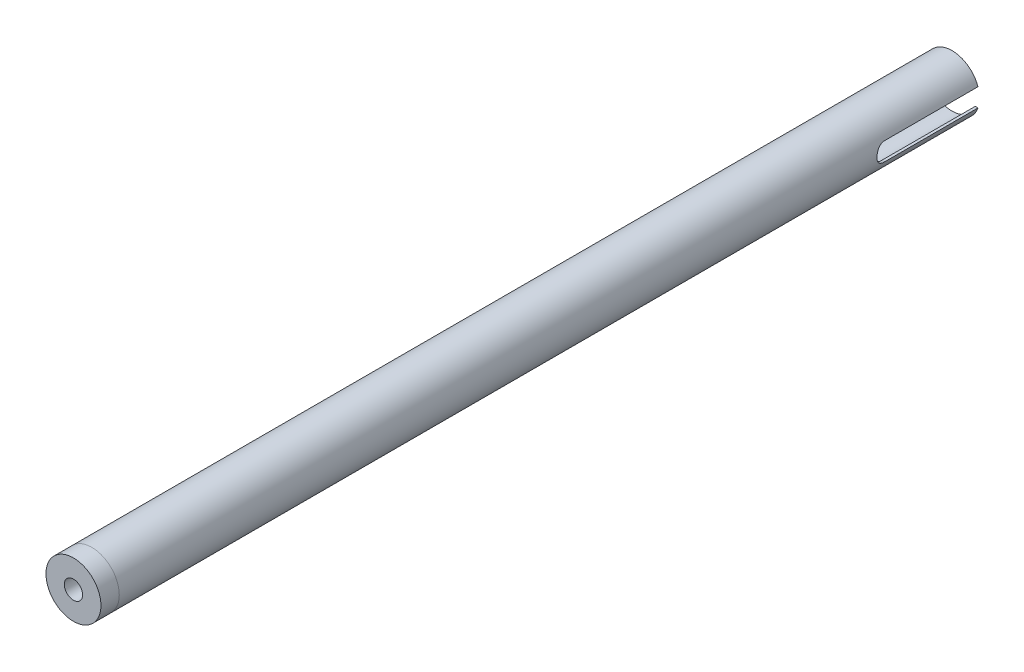
SolidWorks part; units mm, degrees
material "AISI 4130 Steel, normalized at 870C"
ref_plane "Front Plane" through (0, 0, 0) normal (0, 0, 1) x (1, 0, 0)
ref_plane "Top Plane" through (0, 0, 0) normal (0, 1, 0) x (1, 0, 0)
ref_plane "Right Plane" through (0, 0, 0) normal (1, 0, 0) x (0, 0, -1)
sketch "Axis" plane through (0, 0, 0) normal (0, 1, 0) x (1, 0, 0)
  line L0 (0, 0) -> (0, 304.3801) construction
  line L1 (0, 0) -> (0, -21.9075) construction
  line L2 (0, 304.3801) -> (-9.525, 304.3801) construction
  line L4 (0, 332.3201) -> (-22.1542, 267.3343) construction
  point P3 (0, 0)
  dimension "D1" = 21.9075
  dimension "D2" = 9.525
sketch "Sketch1" plane through (0, 0, 0) normal (0, 0, 1) x (1, 0, 0)
  line L0 (-9.525, 0) -> (9.525, 0) construction
  line L1 (-8.9803, 3.175) -> (8.9803, 3.175)
  line L2 (-8.9803, -3.175) -> (8.9803, -3.175)
  circle A0 centre (0, 0) radius 9.525
  circle A1 centre (0, 0) radius 8.636
  circle A2 centre (0, 0) radius 3.175
  dimension "D1" = 19.05
  dimension "D3" = 6.35
  dimension "D2" = 0.889
  dimension "D4" = 6.35
extrude "Threaded insert 1-1" add sketch "Sketch1" against normal blind 6.35 contours A2 L1 A1 | A1 L1 A0 | A2 L0 A1 L1 | A1 L0 A0 L1 | L0 A1 L2 A0 | L0 A2 L2 A1 | A2 L2 A1 | A1 L2 A0 | L0 A1 L2 A2 | L0 A0 L2 A1 | A0 L0 A1 L1 | A1 L0 A2 L1 region at (5.4259, 1.6615, 0) region at (5.4259, -1.6615, 0) region at (8.8881, 1.6046, 0) region at (8.8881, -1.6046, 0) region at (-5.4259, -1.6615, 0) region at (-5.4259, 1.6615, 0) region at (0, 5.4321, 0) region at (0, -5.4321, 0) region at (0, 8.8265, 0) region at (8.5057, -3.3655, 0) region at (-8.8881, -1.6046, 0) region at (-8.8881, 1.6046, 0)
extrude "Threaded insert 1-2" add sketch "Sketch1<3>" against normal blind 6.35 from surface contours A2 L1 A1 | A2 L0 A1 L1 | L0 A2 L2 A1 | A2 L2 A1 | L0 A1 L2 A2 | A1 L0 A2 L1 region at (5.4259, 1.6615, 0) region at (5.4259, -1.6615, 0) region at (-5.4259, -1.6615, 0) region at (-5.4259, 1.6615, 0) region at (0, 5.4321, 0) region at (0, -5.4321, 0) starting at face at (9.525, 0, -6.35)
sketch "Sketch1<3>" plane through (0, 0, 0) normal (0, 0, 1) x (1, 0, 0) same geometry as "Sketch1"
extrude "A-arm tube" add sketch "Sketch1<4>" against normal up to vertex (304.3801 mm away) from surface separate body contours A1 L1 A0 | A1 L0 A0 L1 | L0 A1 L2 A0 | A1 L2 A0 | L0 A0 L2 A1 | A0 L0 A1 L1 region at (8.8881, 1.6046, 0) region at (8.8881, -1.6046, 0) region at (0, 8.8265, 0) region at (8.5057, -3.3655, 0) region at (-8.8881, -1.6046, 0) region at (-8.8881, 1.6046, 0) up to point (0, 0, -304.3801) starting at face at (8.636, 0, -6.35)
sketch "Sketch1<4>" plane through (0, 0, 0) normal (0, 0, 1) x (1, 0, 0) same geometry as "Sketch1"
extrude "Apex slot" cut sketch "Sketch1<5>" along normal blind 35.56 from surface contours A0 L0 A1 L1 | L0 A0 L2 A1 | A1 L0 A0 L1 | L0 A1 L2 A0 region at (8.8881, 1.6046, 0) region at (8.8881, -1.6046, 0) region at (-8.8881, -1.6046, 0) region at (-8.8881, 1.6046, 0) starting at face at (8.636, 0, -304.3801)
sketch "Sketch1<5>" plane through (0, 0, 0) normal (0, 0, 1) x (1, 0, 0) same geometry as "Sketch1"
fillet "Fillet1" radius 3.175 4 edges at (-8.5057, 3.175, -268.8201) (-8.5057, -3.175, -268.8201) (8.5057, -3.175, -268.8201) (8.5057, 3.175, -268.8201)
equation "\"tube diameter\"= 3 / 4"
equation "\"tube thickness\"= .035"
equation "\"apex thickness\"= .25"
equation "\"tube slot\"= 1.4"
equation "\"D1@Sketch1\"=\"tube diameter\""
equation "\"D2@Sketch1\"=\"tube thickness\""
equation "\"threaded insert hole\"= 1 / 4"
equation "\"D3@Sketch1\"=\"threaded insert hole\""
equation "\"D4@Sketch1\"=\"apex thickness\""
equation "\"D1@Apex slot\" = \"tube slot\""
equation "\"D1@Fillet1\"=\"apex thickness\"/2"
equation "\"D2@Axis\"=\"tube diameter\"/2"
